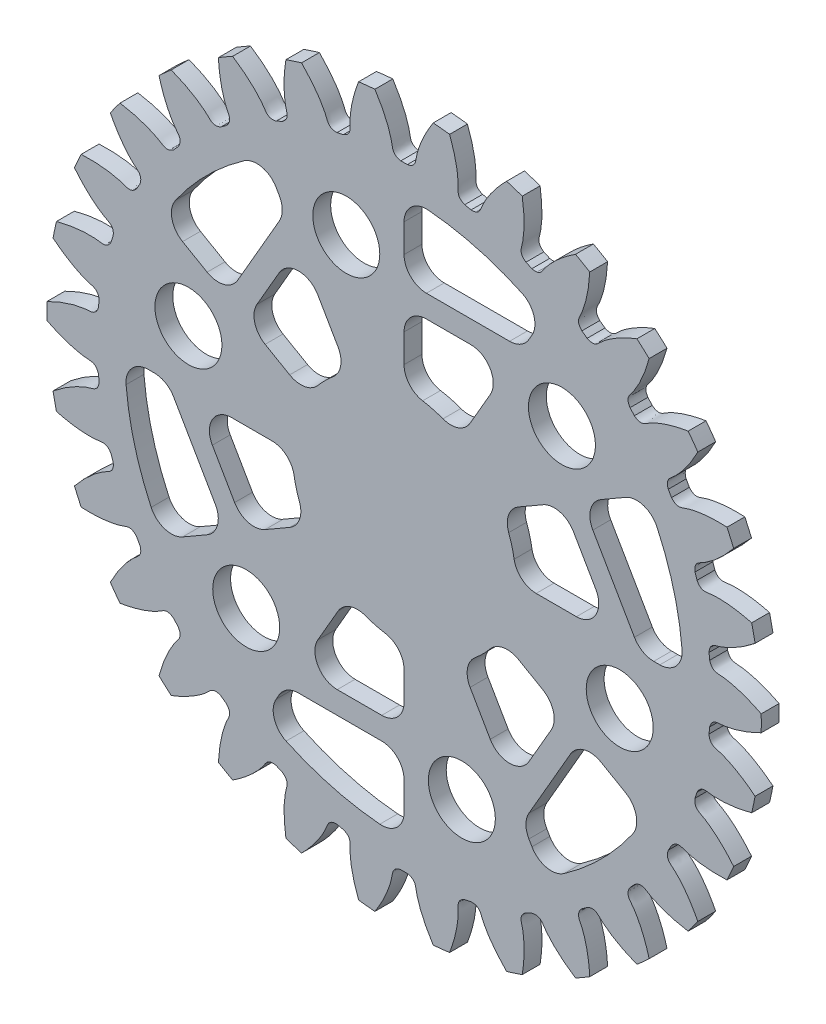
SolidWorks part; units mm, degrees
ref_plane "前视基准面" through (0, 0, 0) normal (0, 0, 1) x (1, 0, 0)
ref_plane "上视基准面" through (0, 0, 0) normal (0, 1, 0) x (1, 0, 0)
ref_plane "右视基准面" through (0, 0, 0) normal (1, 0, 0) x (0, 0, -1)
sketch "草图1" plane through (0, 0, 0) normal (0, 0, 1) x (1, 0, 0)
  circle A0 centre (0, 0) radius 16
extrude "凸台-拉伸1" add sketch "草图1" along normal blind 30
ref_axis "基准轴1" through (0, 0, -1.5) along (0, 0, 1)
sketch "草图2" plane through (0, 0, 0) normal (0, 0, 1) x (1, 0, 0)
  line L0 (0, 0) -> (0, 16) construction
  circle A0 centre (0, 0) radius 16 construction
  arc A1 (0.1456, 13.7492) -> (-0.1456, 13.7492) centre (0, 0) ccw
  arc A2 (3.3663, 18.1906) -> (-3.3663, 18.1906) centre (0, 0) ccw
  spline S0 degree 3 poles (0.1456, 13.7492) (0.5082, 13.813) (0.5103, 14.0471) (0.559, 14.2886) (0.57, 14.3381) (0.5832, 14.3929) (0.5991, 14.4529) (0.6176, 14.518) (0.6391, 14.588) (0.6638, 14.663) (0.6918, 14.7428) (0.7234, 14.8273) (0.7588, 14.9164) (0.7981, 15.01) (0.8416, 15.1079) (0.8894, 15.21) (0.9417, 15.3163) (0.9987, 15.4264) (1.0606, 15.5404) (1.1276, 15.658) (1.1998, 15.779) (1.2774, 15.9034) (1.3605, 16.031) (1.4494, 16.1615) (1.5441, 16.2948) (1.6448, 16.4307) (1.7516, 16.569) (1.8647, 16.7096) (1.9843, 16.8522) (2.1103, 16.9966) (2.2431, 17.1427) (2.3825, 17.2901) (2.5289, 17.4388) (2.6823, 17.5884) (2.8427, 17.7389) (3.0689, 17.9426) (3.2453, 18.0921) (3.3663, 18.1906) knots 0 0 0 0 0.115324 0.123413 0.132512 0.142623 0.153745 0.165878 0.179022 0.193177 0.208343 0.22452 0.241708 0.259907 0.279117 0.299338 0.320571 0.342814 0.366068 0.390334 0.41561 0.441898 0.469196 0.497506 0.526827 0.557158 0.588501 0.620855 0.65422 0.688595 0.723982 0.76038 0.797789 0.836209 0.87564 0.916083 1 1 1 1
  spline S1 degree 3 poles (-0.1456, 13.7492) (-0.5082, 13.813) (-0.5103, 14.0471) (-0.559, 14.2886) (-0.57, 14.3381) (-0.5832, 14.3929) (-0.5991, 14.4529) (-0.6176, 14.518) (-0.6391, 14.588) (-0.6638, 14.663) (-0.6918, 14.7428) (-0.7234, 14.8273) (-0.7588, 14.9164) (-0.7981, 15.01) (-0.8416, 15.1079) (-0.8894, 15.21) (-0.9417, 15.3163) (-0.9987, 15.4264) (-1.0606, 15.5404) (-1.1276, 15.658) (-1.1998, 15.779) (-1.2774, 15.9034) (-1.3605, 16.031) (-1.4494, 16.1615) (-1.5441, 16.2948) (-1.6448, 16.4307) (-1.7516, 16.569) (-1.8647, 16.7096) (-1.9843, 16.8522) (-2.1103, 16.9966) (-2.2431, 17.1427) (-2.3825, 17.2901) (-2.5289, 17.4388) (-2.6823, 17.5884) (-2.8427, 17.7389) (-3.0689, 17.9426) (-3.2453, 18.0921) (-3.3663, 18.1906) knots 0 0 0 0 0.115324 0.123413 0.132512 0.142623 0.153745 0.165878 0.179022 0.193177 0.208343 0.22452 0.241708 0.259907 0.279117 0.299338 0.320571 0.342814 0.366068 0.390334 0.41561 0.441898 0.469196 0.497506 0.526827 0.557158 0.588501 0.620855 0.65422 0.688595 0.723982 0.76038 0.797789 0.836209 0.87564 0.916083 1 1 1 1
extrude "切除-拉伸1" cut sketch "草图2" along normal through all
pattern_circular "阵列(圆周)1" count 30 every 12 about axis through (0, 0, -1.5) along (0, 0, 1) of "切除-拉伸1"
sketch "草图3" plane through (0, 0, 0) normal (0, 0, 1) x (1, 0, 0)
  circle A0 centre (0, 0) radius 15 construction
  dimension "Dn" = 30
sketch "草图4" plane through (0, 0, 30) normal (0, 0, 1) x (1, 0, 0)
  circle A0 centre (0, 0) radius 28.1228
extrude "切除-拉伸2" cut sketch "草图4" against normal blind 29.2
sketch "草图5" plane through (0, 0, 0) normal (0, 0, 1) x (1, 0, 0)
  circle A0 centre (0, 0) radius 2.9
  dimension "D1" = 5.8
extrude "凸台-拉伸2" add sketch "草图5" against normal blind 1.3
sketch "草图8" plane through (0, 0, -1.3) normal (0, 0, -1) x (-1, 0, 0)
  circle A0 centre (0, 0) radius 1.4
  dimension "D1" = 2.8
extrude "凸台-拉伸4" add sketch "草图8" along normal blind 0.7
sketch "草图9" plane through (0, 0, 0) normal (0, 0, -1) x (-1, 0, 0)
  line L0 (0, 5) -> (0, 12.5)
  line L1 (2.5, 4.3301) -> (6.25, 10.8253)
  line L2 (4.3301, 2.5) -> (10.8253, 6.25)
  line L3 (5, 0) -> (12.5, 0)
  line L4 (4.3301, -2.5) -> (10.8253, -6.25)
  line L5 (2.5, -4.3301) -> (6.25, -10.8253)
  line L6 (0, -5) -> (0, -12.5)
  line L7 (-2.5, -4.3301) -> (-6.25, -10.8253)
  line L8 (-4.3301, -2.5) -> (-10.8253, -6.25)
  line L9 (-5, 0) -> (-12.5, 0)
  line L10 (-4.3301, 2.5) -> (-10.8253, 6.25)
  line L11 (-2.5, 4.3301) -> (-6.25, 10.8253)
  line L12 (2.5882, 9.6593) -> (0, 0)
  arc A0 (0, 5) -> (-2.5, 4.3301) centre (0, 0) ccw
  arc A1 (0, 12.5) -> (-6.25, 10.8253) centre (0, 0) ccw
  arc A2 (4.3301, 2.5) -> (2.5, 4.3301) centre (0, 0) ccw
  arc A3 (10.8253, 6.25) -> (6.25, 10.8253) centre (0, 0) ccw
  arc A4 (10.8253, -6.25) -> (12.5, 0) centre (0, 0) ccw
  arc A5 (4.3301, -2.5) -> (5, 0) centre (0, 0) ccw
  arc A6 (0, -5) -> (2.5, -4.3301) centre (0, 0) ccw
  arc A7 (0, -12.5) -> (6.25, -10.8253) centre (0, 0) ccw
  arc A8 (-10.8253, -6.25) -> (-6.25, -10.8253) centre (0, 0) ccw
  arc A9 (-4.3301, -2.5) -> (-2.5, -4.3301) centre (0, 0) ccw
  arc A10 (-4.3301, 2.5) -> (-5, 0) centre (0, 0) ccw
  arc A11 (-10.8253, 6.25) -> (-12.5, 0) centre (0, 0) ccw
  circle A12 centre (0, 0) radius 10 construction
  circle A13 centre (2.5882, 9.6593) radius 1.5
  circle A14 centre (9.6593, 2.5882) radius 1.5
  circle A15 centre (7.0711, -7.0711) radius 1.5
  circle A16 centre (-2.5882, -9.6593) radius 1.5
  circle A17 centre (-9.6593, -2.5882) radius 1.5
  circle A18 centre (-7.0711, 7.0711) radius 1.5
  point P18 (0, 0)
  point P42 (0, 0)
  dimension "D1" = 10
  dimension "D2" = 25
  dimension "D4" = 20
  dimension "D5" = 3
  dimension "D6" = 75
  dimension "D3" = 12
  dimension "D7" = 6
extrude "切除-拉伸5" cut sketch "草图9" against normal blind 10 contours L0 A1 L11 A0 | A18 | L10 A11 L9 A10 | A17 | A9 L8 A8 L7 | A16 | L6 A7 L5 A6 | A15 | A5 L4 A4 L3 | A14 | L2 A3 L1 A2 | A13 region at (2.376, 8.8672, 0) region at (-6.4912, 6.4912, 0) region at (-8.8672, -2.376, 0) region at (-2.376, -8.8672, 0) region at (6.4912, -6.4912, 0) region at (8.8672, 2.376, 0) region at (-3.4755, 8.5029, 0) region at (-9.6593, 2.5882, 0) region at (-7.0711, -7.0711, 0) region at (2.5882, -9.6593, 0) region at (9.6593, -2.5882, 0) region at (7.0711, 7.0711, 0)
sketch "草图10" plane through (0, 0, 0) normal (0, 0, -1) x (-1, 0, 0)
  line L0 (0, 9.1863) -> (0, 8.1863)
  line L2 (-5, 0) -> (-12.5, 0) construction
  line L3 (-7.9555, 4.5931) -> (-10.6074, 0)
  line L4 (-7.0895, 4.0931) -> (-9.4527, 0)
  line L5 (0, 8.1863) -> (-4.7263, 8.1863)
  line L6 (-5.3037, 9.1863) -> (-4.7263, 8.1863)
  line L7 (-10.6074, 0) -> (-9.4527, 0)
  line L8 (-7.9555, 4.5931) -> (-7.0895, 4.0931)
  line L9 (0, 9.1863) -> (-5.3037, 9.1863)
  line L10 (7.9555, 4.5931) -> (7.0895, 4.0931)
  line L11 (7.0895, 4.0931) -> (4.7263, 8.1863)
  line L12 (5.3037, 9.1863) -> (4.7263, 8.1863)
  line L13 (7.9555, 4.5931) -> (5.3037, 9.1863)
  line L14 (7.9555, -4.5931) -> (7.0895, -4.0931)
  line L15 (7.0895, -4.0931) -> (9.4527, 0)
  line L16 (10.6074, 0) -> (9.4527, 0)
  line L17 (7.9555, -4.5931) -> (10.6074, 0)
  line L18 (0, -9.1863) -> (0, -8.1863)
  line L19 (0, -8.1863) -> (4.7263, -8.1863)
  line L20 (5.3037, -9.1863) -> (4.7263, -8.1863)
  line L21 (0, -9.1863) -> (5.3037, -9.1863)
  line L22 (-7.9555, -4.5931) -> (-7.0895, -4.0931)
  line L23 (-7.0895, -4.0931) -> (-4.7263, -8.1863)
  line L24 (-5.3037, -9.1863) -> (-4.7263, -8.1863)
  line L25 (-7.9555, -4.5931) -> (-5.3037, -9.1863)
  point P28 (0, 0)
  dimension "D1" = 6
extrude "凸台-拉伸5" add sketch "草图10" against normal blind 0.8
fillet "圆角1" radius 1 48 edges at (4.3301, 2.5, 0.4) (4.3301, -2.5, 0.4) (-2.5, -4.3301, 0.4) (5, 0, 0.4) (2.5, -4.3301, 0.4) (-10.8253, 6.25, 0.4) (-12.5, 0, 0.4) (-10.8253, -6.25, 0.4) (-6.25, -10.8253, 0.4) (0, -12.5, 0.4) (6.25, -10.8253, 0.4) (-4.3301, -2.5, 0.4) (-4.3301, 2.5, 0.4) (-2.5, 4.3301, 0.4) (12.5, 0, 0.4) (-6.25, 10.8253, 0.4) (-5, 0, 0.4) (0, -5, 0.4) (10.8253, -6.25, 0.4) (10.8253, 6.25, 0.4) (0, 5, 0.4) (2.5, 4.3301, 0.4) (0, 12.5, 0.4) (6.25, 10.8253, 0.4) (-7.0895, -4.0931, 0.4) (-9.4527, 0, 0.4) (-10.6074, 0, 0.4) (-7.9555, -4.5931, 0.4) (-5.3037, -9.1863, 0.4) (0, -8.1863, 0.4) (-4.7263, -8.1863, 0.4) (0, -9.1863, 0.4) (7.9555, -4.5931, 0.4) (5.3037, -9.1863, 0.4) (4.7263, -8.1863, 0.4) (7.0895, -4.0931, 0.4) (10.6074, 0, 0.4) (9.4527, 0, 0.4) (7.9555, 4.5931, 0.4) (7.0895, 4.0931, 0.4) (5.3037, 9.1863, 0.4) (0, 8.1863, 0.4) (4.7263, 8.1863, 0.4) (0, 9.1863, 0.4) (-4.7263, 8.1863, 0.4) (-7.0895, 4.0931, 0.4) (-7.9555, 4.5931, 0.4) (-5.3037, 9.1863, 0.4)
